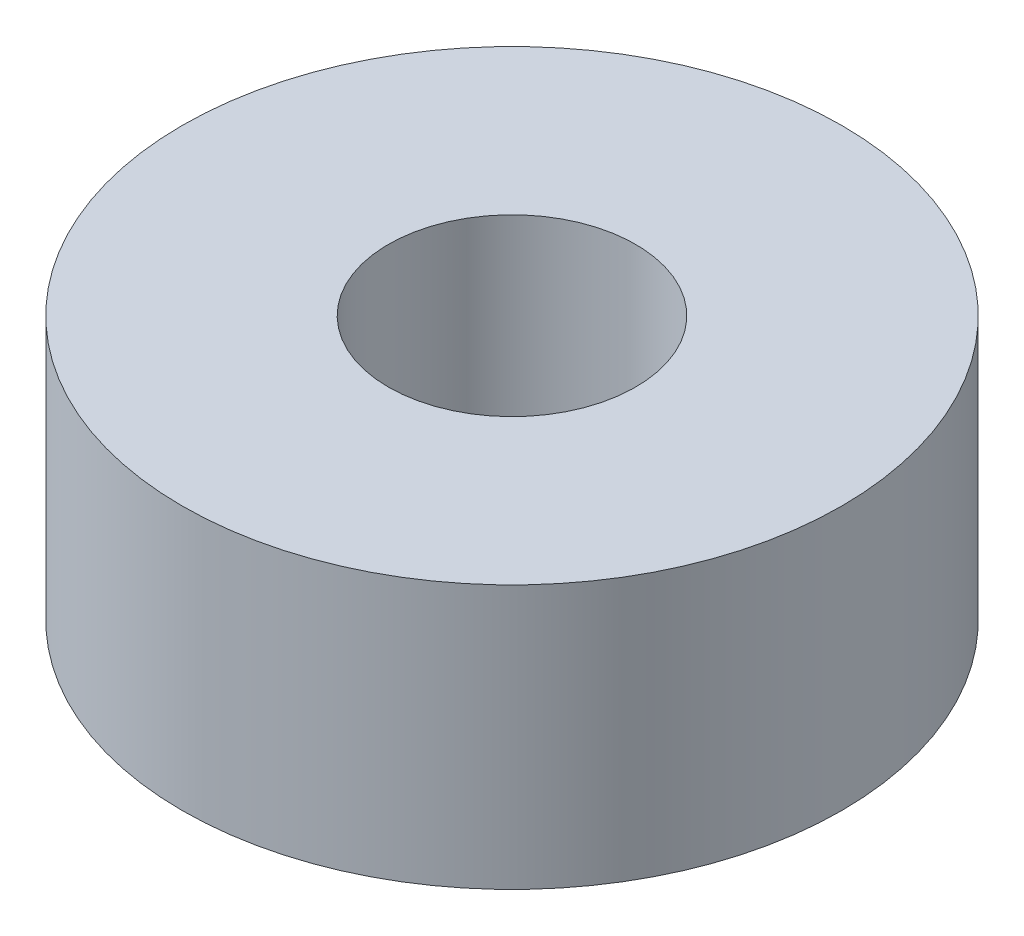
SolidWorks part; units mm, degrees
ref_plane "Front Plane" through (0, 0, 0) normal (0, 0, 1) x (1, 0, 0)
ref_plane "Top Plane" through (0, 0, 0) normal (0, 1, 0) x (1, 0, 0)
ref_plane "Right Plane" through (0, 0, 0) normal (1, 0, 0) x (0, 0, -1)
sketch "Sketch1" plane through (0, 0, 0) normal (0, 1, 0) x (1, 0, 0)
  circle A0 centre (0, 0) radius 20
  dimension "FLANGE_OD" = 40
extrude "Boss-Extrude1" add sketch "Sketch1" along normal blind 16
sketch "Sketch2" plane through (0, 0, 0) normal (0, 1, 0) x (1, 0, 0)
  circle A0 centre (0, 0) radius 7.5
  dimension "BORE_D" = 15
extrude "Cut-Extrude1" cut sketch "Sketch2" along normal through all
sketch "Sketch3" plane through (0, 16, 0) normal (0, 1, 0) x (1, 0, 0)
  circle A0 centre (0, 0) radius 5.282 construction
  circle A1 centre (-5.282, 0) radius 2.0094
  dimension "BOLT_D" = 4.0187
  dimension "BOLT_PCD" = 10.5641
extrude "Cut-Extrude2" cut sketch "Sketch3" against normal blind 11.3743 rebuild error yes
pattern_circular "CirPattern1" count 4 over 360 rebuild error yes
